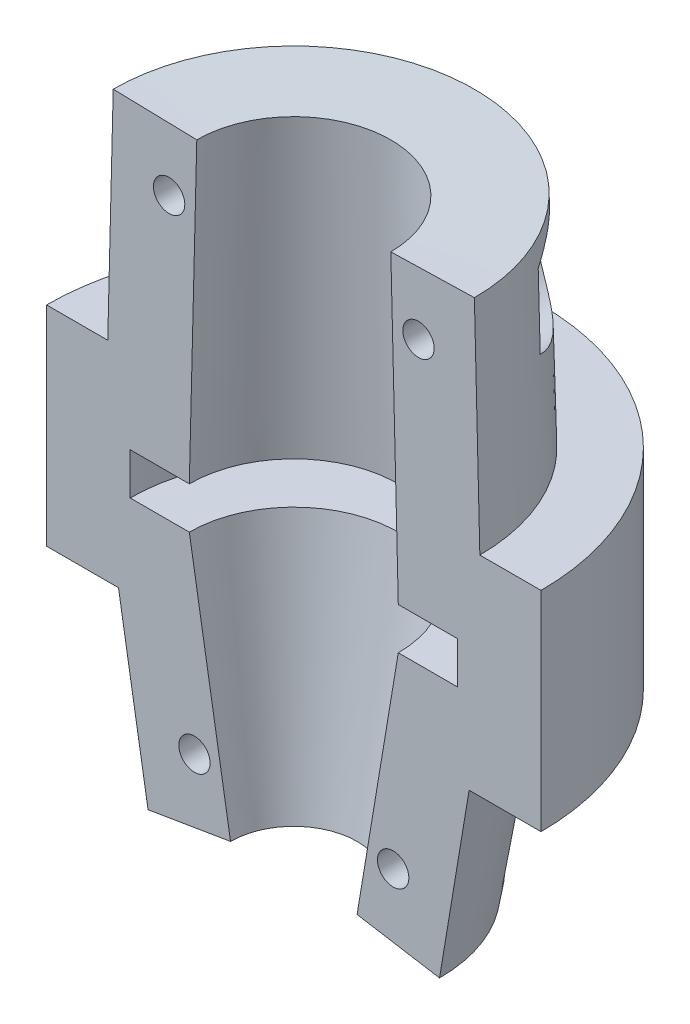
SolidWorks part; units mm, degrees
note: The reader was unsure of these and kept them because the rebuilt part matched: shared geometry of "Sketch27<5>".
ref_plane "Front Plane" through (0, 0, 0) normal (0, 0, 1) x (1, 0, 0)
ref_plane "Top Plane" through (0, 0, 0) normal (0, 1, 0) x (1, 0, 0)
ref_plane "Right Plane" through (0, 0, 0) normal (1, 0, 0) x (0, 0, -1)
sketch "Sketch1" plane through (0, 0, 0) normal (0, 0, 1) x (1, 0, 0)
  line L0 (0, 0) -> (0, 27.838) construction
  line L1 (6.9734, -3.1046) -> (8.3885, 5.3858)
  line L2 (3.0279, -2.4471) -> (5, 9.3858)
  line L3 (5, 9.3858) -> (7.8293, 9.3858)
  line L4 (7.8293, 9.3858) -> (7.8293, 11.3858)
  line L5 (7.8293, 11.3858) -> (5, 11.3858)
  line L6 (5, 11.3858) -> (4.6419, 25.8213)
  line L7 (8.3885, 5.3858) -> (11.8293, 5.3858)
  line L8 (11.8293, 5.3858) -> (11.8293, 15.3858)
  line L9 (11.8293, 15.3858) -> (8.902, 15.3858)
  line L10 (8.902, 15.3858) -> (8.6406, 25.9205)
  line L11 (3.0279, -2.4471) -> (6.9734, -3.1046)
  line L12 (4.6419, 25.8213) -> (8.6406, 25.9205)
  line L13 (3.0279, -2.4471) -> (5, 9.3858) construction
  line L14 (4.9758, 12.361) -> (3.0048, 91.806) construction
  dimension "D1" = 2
  dimension "D2" = 4
revolve "Revolve1" add sketch "Sketch1" angle 180 about L0
sketch "Sketch27" plane through (0, 0, 0) normal (0, 0, 1) x (1, 0, 0)
  line L0 (4.6419, 25.8213) -> (5, 11.3858) construction
  line L1 (8.6406, 25.9205) -> (4.6419, 25.8213) construction
  line L2 (0, 27.1191) -> (0, -2.2836) construction
  line L3 (-11.8293, 10.3858) -> (11.8293, 10.3858) construction
  line L4 (-11.8293, 5.3858) -> (-11.8293, 15.3858) construction
  line L5 (11.8293, 5.3858) -> (11.8293, 15.3858) construction
  line L6 (5, 9.3858) -> (3.0279, -2.4471) construction
  line L7 (3.0279, -2.4471) -> (6.9734, -3.1046) construction
  circle A0 centre (5.9659, 22.8532) radius 0.75
  circle A1 centre (5.9659, 22.8532) radius 2.5
  circle A2 centre (-5.9659, 22.8532) radius 2.5
  circle A3 centre (-5.9659, 22.8532) radius 0.75
  circle A4 centre (4.754, 0.3066) radius 0.75
  circle A5 centre (4.754, 0.3066) radius 2.5
  circle A6 centre (-4.754, 0.3066) radius 2.5
  circle A7 centre (-4.754, 0.3066) radius 0.75
  dimension "D1" = 1.5
  dimension "D3" = 5
  dimension "D5" = 1.5
  dimension "D6" = 5
  dimension "D2" = 1.25
  dimension "D4" = 3
  dimension "D7" = 1.25
  dimension "D8" = 3
extrude "Cut-Extrude5" cut sketch "Sketch27" against normal through all contours A0 | A3 | A4 | A7
extrude "Cut-Extrude6" cut sketch "Sketch27<5>" against normal blind 10 from offset 4 offset against normal yes
sketch "Sketch27<5>" plane through (0, 0, 0) normal (0, 0, 1) x (1, 0, 0) same geometry as "Sketch27"
ref_plane "Plane1" through (0, 2.3465, 4.0642) normal (0, 0.5, 0.866) x (-1, 0, 0)
ref_plane "Plane2" through (0, 0, -20) normal (0, 0, 1) x (1, 0, 0)
